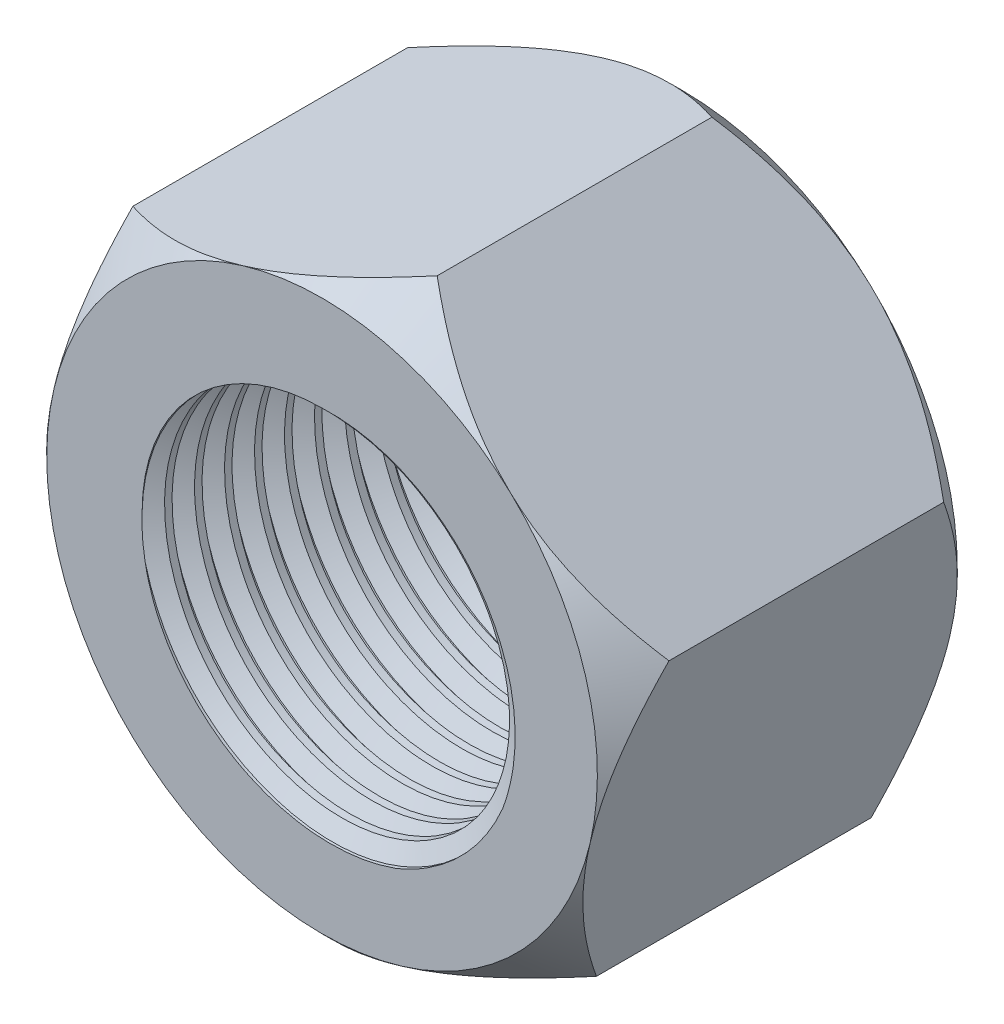
SolidWorks part; units mm, degrees
ref_plane "Front Plane" through (0, 0, 0) normal (0, 0, 1) x (1, 0, 0)
ref_plane "Top Plane" through (0, 0, 0) normal (0, 1, 0) x (1, 0, 0)
ref_plane "Right Plane" through (0, 0, 0) normal (1, 0, 0) x (0, 0, -1)
sketch "Sketch1" plane through (0, 0, 0) normal (0, 0, 1) x (1, 0, 0)
  line L1 (-1.9322, 1.8136) -> (-2.5367, -0.7665)
  line L2 (-2.5367, -0.7665) -> (-0.6046, -2.5801)
  line L3 (-0.6046, -2.5801) -> (1.9322, -1.8136)
  line L4 (1.9322, -1.8136) -> (2.5367, 0.7665)
  line L5 (2.5367, 0.7665) -> (0.6046, 2.5801)
  line L6 (0.6046, 2.5801) -> (-1.9322, 1.8136)
  circle A0 centre (0, 0) radius 2.295 construction
  circle A2 centre (0, 0) radius 1.5
  dimension "D2" = 3
  dimension "D1" = 5.3
extrude "Boss-Extrude1" add sketch "Sketch1" along normal mid plane 3
sketch "Sketch2" plane through (0, 0, 1.5) normal (0, 0, 1) x (1, 0, 0)
  circle A0 centre (0, 0) radius 2.295
extrude "Cut-Extrude2" cut sketch "Sketch2" against normal blind 5 draft 45 flip side to cut contours A0
mirror "Mirror3" about plane through (0, 0, 0) normal (0, 0, 1) of "Cut-Extrude2"
thread "Thread1" pitch 0.25 method cut profile "Thread Profile1" start angle 0, offset 3, length 10, pitch 0.25, diameter 3
ref_plane "Plane1" through (-1.5, 0, 4.5) normal (0, -1, 0) x (-1, 0, 0)
sketch "Thread Profile1" plane through (-1.5, 0, 4.5) normal (0, -1, 0) x (-1, 0, 0)
  line L0 (0, 0) -> (0, 0.25) construction
  line L1 (0, 0) -> (0.1353, 0.0781)
  line L2 (0.1353, 0.0781) -> (0.1353, 0.1094)
  line L3 (0.1353, 0.1094) -> (0, 0.1875)
  line L4 (0.1353, 0.0937) -> (0, 0.0937) construction
  line L11 (0, 0) -> (0, 0.1875)
  point P2 (0, 0)
  dimension "Pitch" = 0.25
  dimension "Profile_Angle" = 60
  dimension "Profile_Land" = 0.0312
  dimension "Profile_Height" = 0.1353
